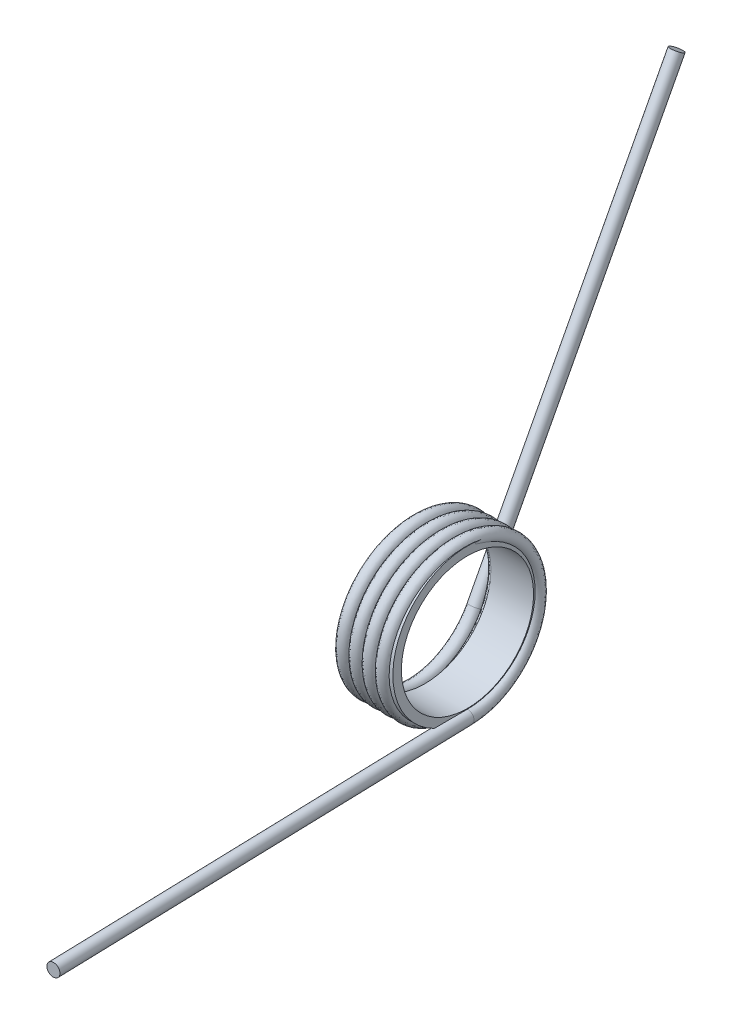
SolidWorks part; units mm, degrees
ref_plane "Front" through (0, 0, 0) normal (0, 0, 1) x (1, 0, 0)
ref_plane "Top" through (0, 0, 0) normal (0, 1, 0) x (1, 0, 0)
ref_plane "Right" through (0, 0, 0) normal (1, 0, 0) x (0, 0, -1)
sketch "Sketch1" plane through (0, 0, 0) normal (1, 0, 0) x (0, 0, -1)
  line L0 (0, -3.9751) -> (0, -4.7371) construction
  line L1 (4.1024, -2.3686) -> (16.8024, 19.6285) construction
  line L2 (0, -4.7371) -> (-25.4, -4.7371) construction
  line L3 (0, 0) -> (4.7371, 0) construction
  line L4 (0, 0) -> (4.1024, -2.3686) construction
  line L5 (-25.4, -4.7371) -> (-25.4, -3.9751) construction
  line L6 (-25.4, -3.9751) -> (0, -3.9751) construction
  line L7 (16.8024, 19.6285) -> (16.1425, 20.0095) construction
  line L8 (16.1425, 20.0095) -> (3.4425, -1.9876) construction
  circle A0 centre (0, 0) radius 4.7371 construction
  circle A1 centre (0, 0) radius 3.175 construction
  circle A2 centre (0, 0) radius 4.3561 construction
  point P7 (0, -4.3561)
  point P10 (0, 4.7371)
  dimension "OD" = 9.4742
  dimension "For Shaft Diameter" = 6.35
  dimension "Wire Diameter" = 0.762
  dimension "Leg Length" = 25.4
  dimension "Deflection Angle" = 120
sketch "Sketch2" plane through (0, 0, 0) normal (1, 0, 0) x (0, 0, -1)
  circle A0 centre (0, 0) radius 4.3561 construction
  circle A2 centre (0, 0) radius 4.3561
curve "Helix/Spiral1" pitch 0.7874 height 3.2808 turns 4.1667
ref_plane "Plane1" through (0, -4.3561, 0) normal (-0.0288, 0, -0.9996) x (0.9993, -0.0232, -0.0287)
sketch "Sketch3" plane through (0, -4.3561, 0) normal (-0.0288, 0, -0.9996) x (0.9993, -0.0232, -0.0287)
  circle A0 centre (0, 0) radius 0.381
  dimension "D1" = 0.762
sweep "Sweep1" add profiles "Sketch3" path "Helix/Spiral1"
sketch "Sketch4" plane through (0, 0, 0) normal (0.0288, 0, 0.9996) x (-0.9993, 0.0232, 0.0287)
  circle A1 centre (-0.1012, 4.3549) radius 0.381
  circle A2 centre (-0.1012, 4.3549) radius 0.381
  dimension "D1" = 0
extrude "Extrude1" add sketch "Sketch4" along normal blind 25.4
sketch "Sketch5" plane through (-0.0027, 0.0817, -0.0472) normal (-0.0288, 0.8657, -0.4998) x (0.9996, 0.0249, -0.0143)
  circle A1 centre (-3.2796, 4.356) radius 0.381
  circle A2 centre (-3.2796, 4.356) radius 0.381
  dimension "D1" = 0
extrude "Extrude2" add sketch "Sketch5" along normal blind 25.4
sketch "Sketch6" plane through (0, 0, 0) normal (1, 0, 0) x (0, 0, -1)
  circle A2 centre (0, 0) radius 3.9751 construction
sketch "Sketch7" plane through (0, 0, 0) normal (1, 0, 0) x (0, 0, -1)
  circle A0 centre (0, 0) radius 3.937
  circle A1 centre (0, 0) radius 4.445
  dimension "D1" = 7.874
  dimension "D2" = 0.508
extrude "Boss-Extrude1" add sketch "Sketch7" against normal blind 2.54
sketch "Sketch8" plane through (0, 0, 0) normal (0, 1, 0) x (1, 0, 0)
  line L0 (0.3808, 0.011) -> (-3.681, 0.011) construction
equation "\"D4@Helix/Spiral1\" = \"Wire Diameter@Sketch1\" + .001"
equation "\"D1@Sketch3\"=\"Wire Diameter@Sketch1\""
equation "\"D1@Extrude2\"=\"Leg Length@Sketch1\""
equation "\"Leg Length@Extrude1\"=\"Leg Length@Sketch1\""
